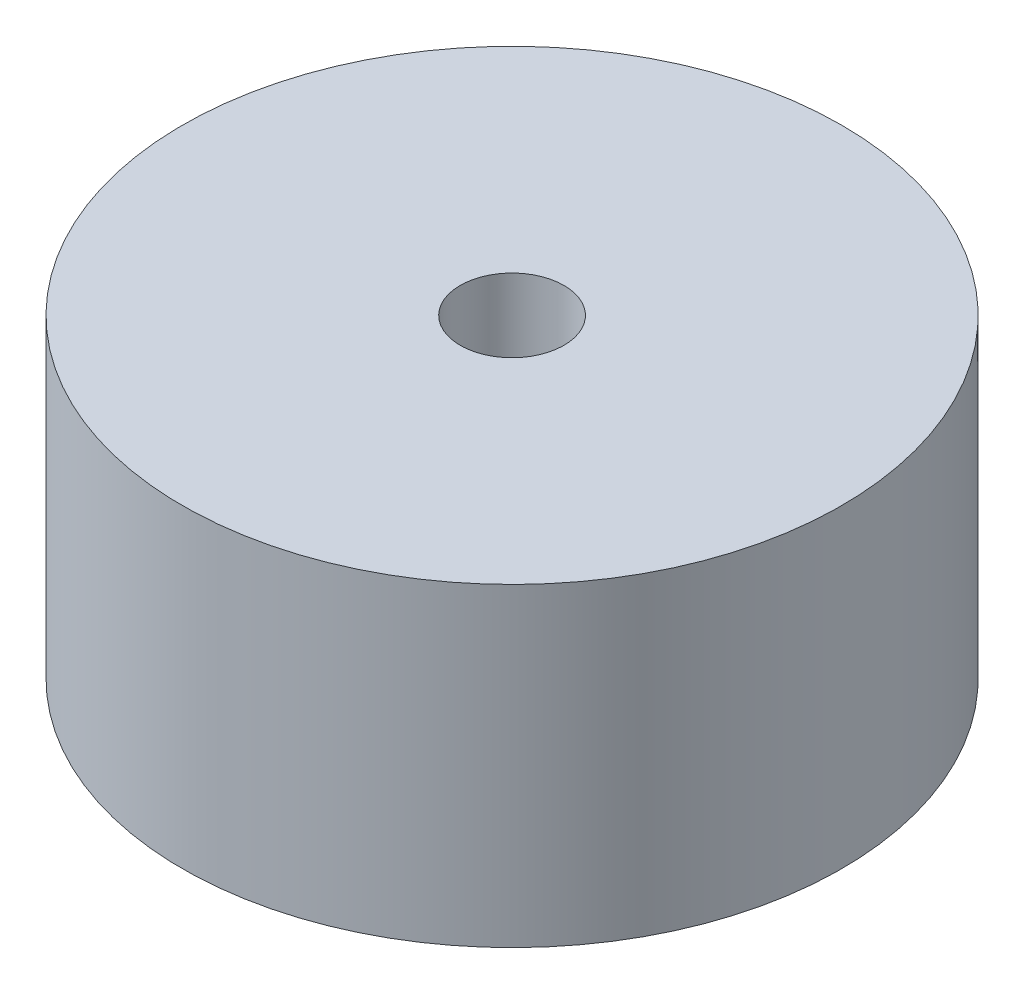
SolidWorks part; units mm, degrees
ref_plane "Front Plane" through (0, 0, 0) normal (0, 0, 1) x (1, 0, 0)
ref_plane "Top Plane" through (0, 0, 0) normal (0, 1, 0) x (1, 0, 0)
ref_plane "Right Plane" through (0, 0, 0) normal (1, 0, 0) x (0, 0, -1)
sketch "Sketch1" plane through (0, 0, 0) normal (0, 1, 0) x (1, 0, 0)
  circle A0 centre (0, 0) radius 31.75
  dimension "D1" = 63.5
extrude "Boss-Extrude1" add sketch "Sketch1" along normal blind 30.3
sketch "Sketch2" plane through (0, 0, 0) normal (0, -1, 0) x (1, 0, 0)
  circle A0 centre (0, 0) radius 5
  dimension "D1" = 10
extrude "Cut-Extrude1" cut sketch "Sketch2" against normal through all
